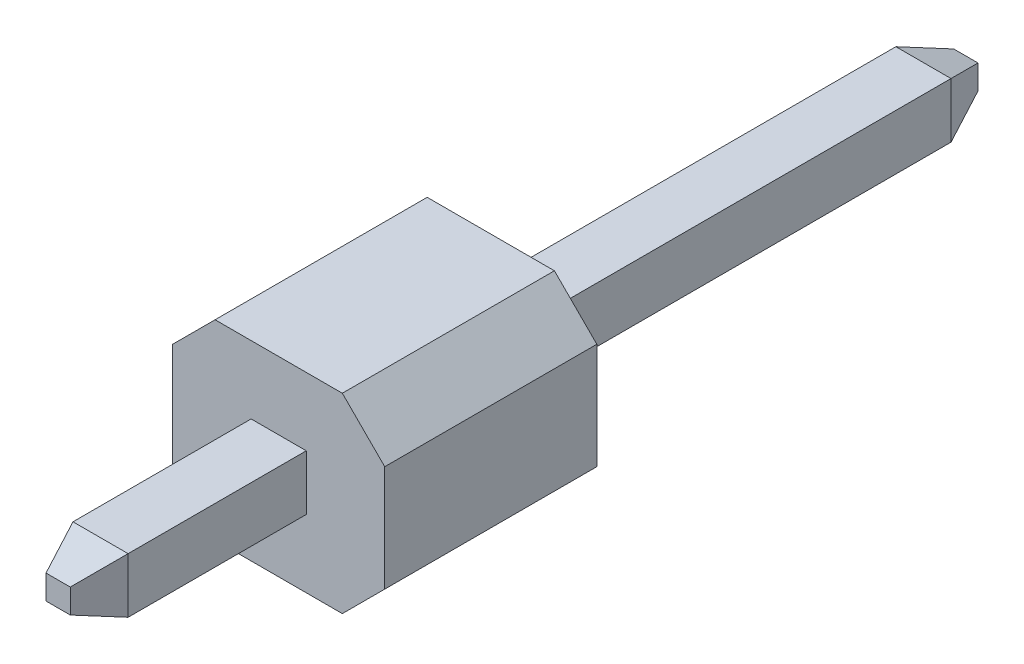
SolidWorks part; units mm, degrees
ref_plane "Front Plane" through (0, 0, 0) normal (0, 0, 1) x (1, 0, 0)
ref_plane "Top Plane" through (0, 0, 0) normal (0, 1, 0) x (1, 0, 0)
ref_plane "Right Plane" through (0, 0, 0) normal (1, 0, 0) x (0, 0, -1)
sketch "Sketch1" plane through (0, 0, 0) normal (0, 0, 1) x (1, 0, 0)
  line L1 (1.25, -1.125) -> (-1.25, -1.125)
  line L2 (1.25, -1.125) -> (1.25, 1.125)
  line L3 (1.25, 1.125) -> (-1.25, 1.125)
  line L4 (-1.25, -1.125) -> (-1.25, 1.125)
  line L5 (1.25, -1.125) -> (-1.25, 1.125) construction
  line L6 (1.25, 1.125) -> (-1.25, -1.125) construction
  point P0 (0, 0)
  dimension "D1" = 2.25
  dimension "D2" = 2.5
extrude "Boss-Extrude1" add sketch "Sketch1" along normal mid plane 2.5
sketch "Sketch2" plane through (0, 0, 0) normal (0, 0, 1) x (1, 0, 0)
  line L1 (0.325, -0.325) -> (-0.325, -0.325)
  line L2 (0.325, -0.325) -> (0.325, 0.325)
  line L3 (0.325, 0.325) -> (-0.325, 0.325)
  line L4 (-0.325, -0.325) -> (-0.325, 0.325)
  line L5 (0.325, -0.325) -> (-0.325, 0.325) construction
  line L6 (0.325, 0.325) -> (-0.325, -0.325) construction
  circle A0 centre (0, 0) radius 0.325 construction
  dimension "D1" = 0.65
extrude "Boss-Extrude2" add sketch "Sketch2" along normal blind 3.35 and the other way blind 6.35
sketch "Sketch3" plane through (0, 0, -6.35) normal (0, 0, -1) x (-1, 0, 0)
  line L1 (0.325, -0.325) -> (-0.325, -0.325)
  line L2 (0.325, -0.325) -> (0.325, 0.325)
  line L3 (0.325, 0.325) -> (-0.325, 0.325)
  line L4 (-0.325, -0.325) -> (-0.325, 0.325)
  line L5 (0.325, -0.325) -> (-0.325, 0.325) construction
  line L6 (0.325, 0.325) -> (-0.325, -0.325) construction
  point P0 (0, 0)
extrude "Boss-Extrude3" add sketch "Sketch3" along normal blind 0.5 draft 20
sketch "Sketch5" plane through (0, 0, 3.35) normal (0, 0, 1) x (1, 0, 0)
  line L0 (0.325, -0.325) -> (-0.325, 0.325) construction
  line L1 (-0.325, -0.325) -> (0.325, 0.325) construction
  line L2 (0.325, 0.325) -> (-0.325, 0.325) construction
  point P9 (0, 0)
sketch "Sketch7" plane through (0, 0, 3.35) normal (0, 0, 1) x (1, 0, 0)
  line L4 (-0.325, 0.325) -> (-0.325, -0.325)
  line L5 (-0.325, -0.325) -> (0.325, -0.325)
  line L6 (0.325, -0.325) -> (0.325, 0.325)
  line L7 (0.325, 0.325) -> (-0.325, 0.325)
  line L8 (-0.325, 0.325) -> (-0.325, -0.325)
  line L9 (-0.325, -0.325) -> (0.325, -0.325)
  line L10 (0.325, -0.325) -> (0.325, 0.325)
  line L11 (0.325, 0.325) -> (-0.325, 0.325)
  dimension "D1" = 0
extrude "Boss-Extrude6" add sketch "Sketch7" along normal blind 0.5 draft 20
chamfer "Chamfer1" distance 0.5 angle 45 4 edges at (-1.25, -1.125, 0) (1.25, -1.125, 0) (1.25, 1.125, 0) (-1.25, 1.125, 0)
